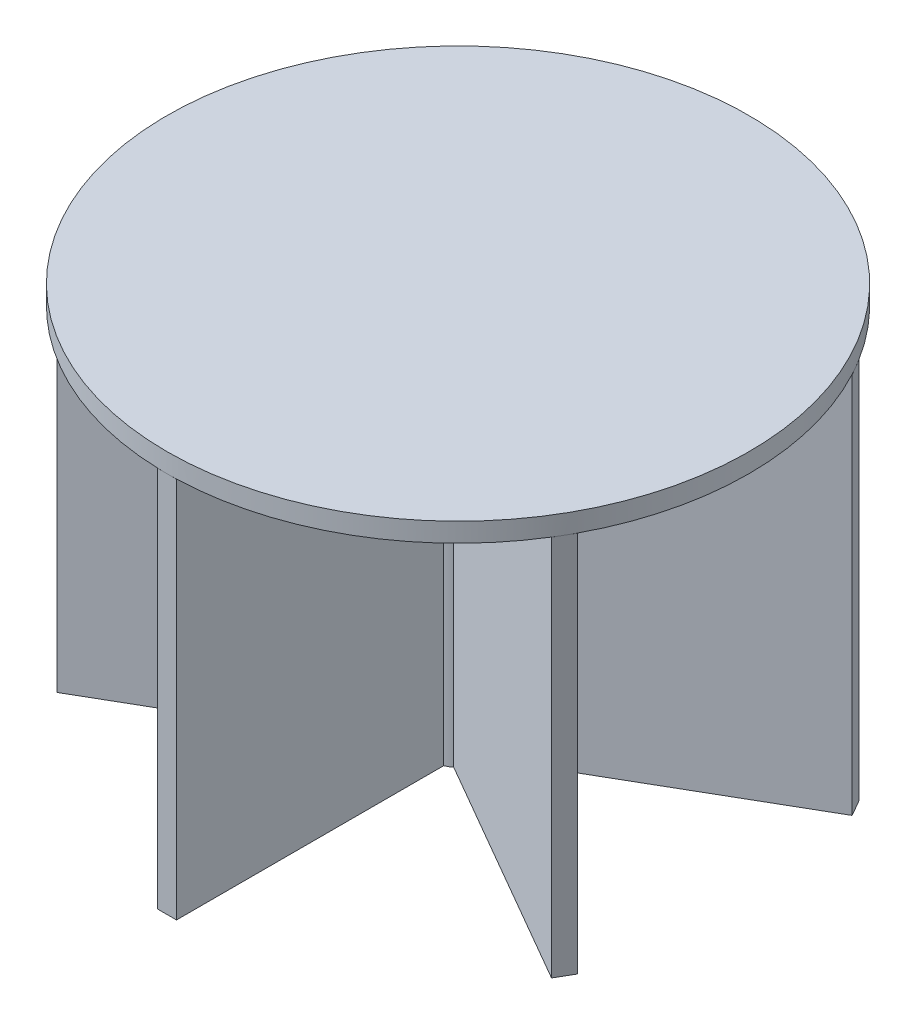
SolidWorks part; units mm, degrees
ref_plane "Front Plane" through (0, 0, 0) normal (0, 0, 1) x (1, 0, 0)
ref_plane "Top Plane" through (0, 0, 0) normal (0, 1, 0) x (1, 0, 0)
ref_plane "Right Plane" through (0, 0, 0) normal (1, 0, 0) x (0, 0, -1)
sketch "Sketch1" plane through (0, 0, 0) normal (0, 1, 0) x (1, 0, 0)
  line L2 (-1.27, 3.175) -> (-1.27, 38.735)
  line L3 (-1.27, 38.735) -> (1.27, 38.735)
  line L4 (1.27, 3.175) -> (1.27, 38.735)
  line L5 (2.1146, 2.6874) -> (32.9105, 20.4674)
  line L6 (32.9105, 20.4674) -> (34.1805, 18.2676)
  line L7 (3.3846, 0.4876) -> (34.1805, 18.2676)
  line L9 (3.3846, -0.4876) -> (34.1805, -18.2676)
  line L10 (34.1805, -18.2676) -> (32.9105, -20.4674)
  line L11 (2.1146, -2.6874) -> (32.9105, -20.4674)
  line L13 (1.27, -3.175) -> (1.27, -38.735)
  line L14 (1.27, -38.735) -> (-1.27, -38.735)
  line L15 (-1.27, -3.175) -> (-1.27, -38.735)
  line L17 (-2.1146, -2.6874) -> (-32.9105, -20.4674)
  line L18 (-32.9105, -20.4674) -> (-34.1805, -18.2676)
  line L19 (-3.3846, -0.4876) -> (-34.1805, -18.2676)
  line L21 (-3.3846, 0.4876) -> (-34.1805, 18.2676)
  line L22 (-34.1805, 18.2676) -> (-32.9105, 20.4674)
  line L23 (-2.1146, 2.6874) -> (-32.9105, 20.4674)
  arc A0 (-3.3846, 0.4876) -> (-3.3846, -0.4876) centre (0, 0) ccw
  arc A1 (-1.27, 3.175) -> (-2.1146, 2.6874) centre (0, 0) ccw
  arc A2 (2.1146, 2.6874) -> (1.27, 3.175) centre (0, 0) ccw
  arc A3 (3.3846, -0.4876) -> (3.3846, 0.4876) centre (0, 0) ccw
  arc A4 (1.27, -3.175) -> (2.1146, -2.6874) centre (0, 0) ccw
  arc A5 (-2.1146, -2.6874) -> (-1.27, -3.175) centre (0, 0) ccw
  point P4 (0, 38.735)
  point P28 (0, 0)
  point P29 (0, -38.735)
  dimension "D1" = 2.54
  dimension "D2" = 35.56
  dimension "D3" = 3.175
  dimension "D4" = 6
extrude "Boss-Extrude1" add sketch "Sketch1" along normal blind 50.8
sketch "Sketch2" plane through (0, 50.8, 0) normal (0, 1, 0) x (1, 0, 0)
  line L0 (-32.9105, 20.4674) -> (-34.1805, 18.2676) construction
  circle A0 centre (0, 0) radius 38.735
extrude "Boss-Extrude2" add sketch "Sketch2" along normal blind 2.54
